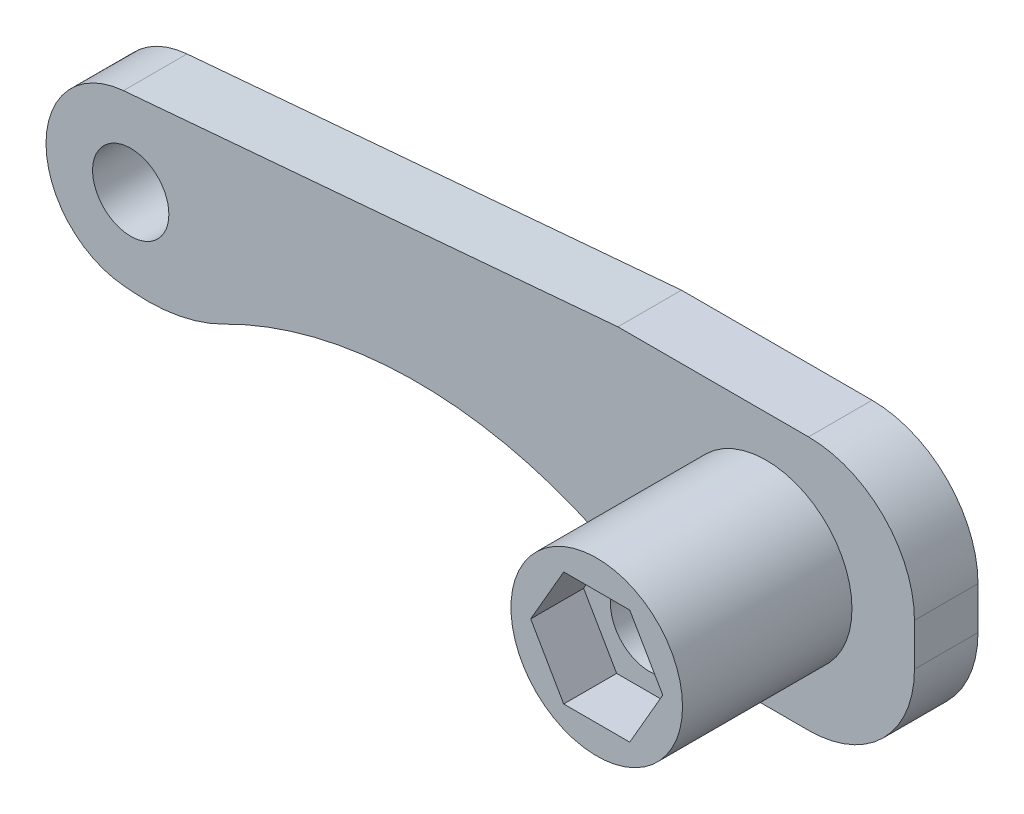
SolidWorks part; units mm, degrees
ref_plane "Front Plane" through (0, 0, 0) normal (0, 0, 1) x (1, 0, 0)
ref_plane "Top Plane" through (0, 0, 0) normal (0, 1, 0) x (1, 0, 0)
ref_plane "Right Plane" through (0, 0, 0) normal (1, 0, 0) x (0, 0, -1)
sketch "Sketch1" plane through (0, 0, 0) normal (0, 0, 1) x (1, 0, 0)
  line L0 (-7, 6) -> (-30.344, 3.9852)
  line L1 (-7, -6) -> (7, -6)
  line L2 (-7, -6) -> (-7, 6)
  line L3 (-7, 6) -> (7, 6)
  line L4 (7, -6) -> (7, 6)
  line L5 (-7, -6) -> (7, 6) construction
  line L6 (-7, 6) -> (7, -6) construction
  line L7 (9.3726, 0) -> (-57.9404, 0) construction
  line L8 (-7, -6) -> (-30.344, -3.9852)
  circle A0 centre (0, 0) radius 4.05
  arc A1 (-30.344, 3.9852) -> (-30.344, -3.9852) centre (-30, 0) ccw
  circle A2 centre (-30, 0) radius 1.8
  point P0 (0, 0)
  dimension "D2" = 8.1
  dimension "D5" = 4
  dimension "D6" = 3.6
  dimension "D1" = 12
  dimension "D3" = 14
  dimension "D4" = 30
extrude "Boss-Extrude1" add sketch "Sketch1" along normal blind 3 contours L1 L4 L3 L2 A0 | L0 A1 L8 L2 region at (-18.6617, 0, 0) region at (0, 5.8156, 0)
extrude "Boss-Extrude2" add sketch "Sketch1<2>" along normal blind 11 contours A0 region at (0, 0, 0)
sketch "Sketch1<2>" plane through (0, 0, 0) normal (0, 0, 1) x (1, 0, 0) same geometry as "Sketch1"
fillet "Fillet1" radius 5 2 edges at (7, -6, 1.5) (7, 6, 1.5)
sketch "Sketch2" plane through (0, 0, 0) normal (0, 0, -1) x (-1, 0, 0)
  circle A0 centre (0, 0) radius 1.85
  dimension "D1" = 3.7
extrude "Cut-Extrude1" cut sketch "Sketch2" against normal through all
sketch "Sketch3" plane through (0, 0, 11) normal (0, 0, 1) x (1, 0, 0)
  line L1 (1.5588, 2.7) -> (-1.5588, 2.7)
  line L2 (-1.5588, 2.7) -> (-3.1177, 0)
  line L3 (-3.1177, 0) -> (-1.5588, -2.7)
  line L4 (-1.5588, -2.7) -> (1.5588, -2.7)
  line L5 (1.5588, -2.7) -> (3.1177, 0)
  line L6 (3.1177, 0) -> (1.5588, 2.7)
  circle A0 centre (0, 0) radius 2.7 construction
  point P1 (0, 0)
  dimension "D1" = 5.4
extrude "Cut-Extrude2" cut sketch "Sketch3" against normal blind 2.5
sketch "Sketch5" plane through (0, 0, 3) normal (0, 0, 1) x (1, 0, 0)
  line L0 (-7, -6) -> (-30.344, -3.9852) construction
  line L1 (-7, -6) -> (2, -6) construction
  line L2 (-7, -6) -> (-3.278, -6)
  line L3 (-7, -6) -> (-27.4109, -4.2383)
  arc A0 (-27.4109, -4.2383) -> (-3.2712, -6) centre (-16.5, -21) cw
  line M5 (-7, -6) -> (2, -6)
  line M12 (-30.344, -3.9852) -> (-7, -6)
  dimension "D1" = 20
  dimension "D2" = 21
  dimension "D3" = 16.5
extrude "Cut-Extrude3" cut sketch "Sketch5" against normal through all and the other way through all contours A0 M12 M5 region at (-15.0974, -3.5677, 3)
fillet "Fillet2" radius 8 2 edges at (-3.2712, -6, 1.5) (-27.4109, -4.2383, 1.5)
